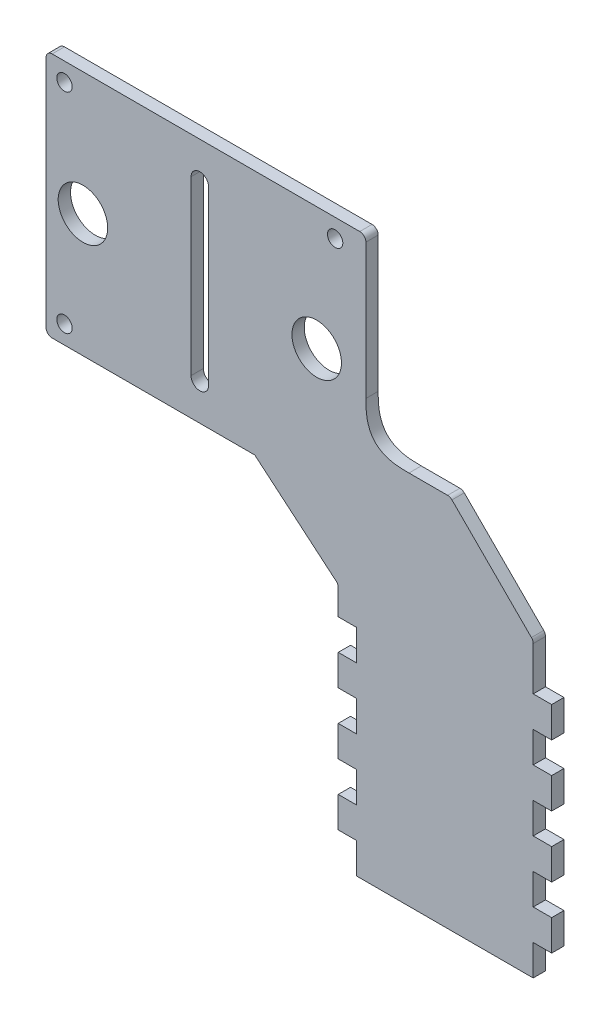
SolidWorks part; units mm, degrees
ref_plane "Front Plane" through (0, 0, 0) normal (0, 0, 1) x (1, 0, 0)
ref_plane "Top Plane" through (0, 0, 0) normal (0, 1, 0) x (1, 0, 0)
ref_plane "Right Plane" through (0, 0, 0) normal (1, 0, 0) x (0, 0, -1)
sketch "Sketch1" plane through (0, 0, 0) normal (0, 0, 1) x (1, 0, 0)
  line L0 (33.9359, 0) -> (47, -11)
  line L1 (0, 0) -> (50, 0)
  line L2 (0, 0) -> (0, 40)
  line L3 (0, 40) -> (50, 40)
  line L4 (50, 0) -> (50, 40)
  line L5 (50, 0) -> (79.2, 0)
  line L6 (50, 0) -> (50, -51)
  line L7 (50, -51) -> (79.2, -51)
  line L8 (79.2, 0) -> (79.2, -51)
  line L9 (50, 0) -> (79.2, 0)
  line L12 (79.2, 0) -> (79.2, -21)
  line L13 (79.2, 0) -> (50, 0)
  line L14 (79.2, 0) -> (79.2, 10)
  line L15 (79.2, 10) -> (50, 10)
  line L16 (50, 0) -> (50, 10)
  line L17 (40, 0) -> (50, 0)
  line L18 (40, 0) -> (40, -5)
  line L19 (40, -5) -> (50, -5)
  line L20 (50, 0) -> (50, -5)
  line L21 (50, -5) -> (44, -5)
  line L22 (50, -5) -> (50, -11)
  line L23 (50, -11) -> (44, -11)
  line L24 (44, -5) -> (44, -11)
  line L26 (50, 10) -> (52, 10)
  line L27 (50, 10) -> (50, 40)
  line L28 (50, 40) -> (52, 40)
  line L29 (52, 10) -> (52, 40)
  dimension "D1" = 50
  dimension "D2" = 40
  dimension "D3" = 29.2
  dimension "D4" = 51
  dimension "D5" = 0
  dimension "D6" = 10
  dimension "D7" = 0
  dimension "D8" = 0
  dimension "D9" = 0
  dimension "D10" = 10
  dimension "D11" = 5
  dimension "D12" = 0
  dimension "D13" = 0
  dimension "D14" = 6
  dimension "D15" = 6
  dimension "D16" = 2
  dimension "D17" = 3
extrude "plate_body" add sketch "Sketch1" along normal blind 2 contours L1 L4 L3 L2 | L8 L5 L1 L6 L7 | L14 L15 L4 L5 | L18 L19 L6 L1 | L19 L6 | L15 L29 L28 L4 | L18 L1 L0 | L24 L19 L0 region at (39.4486, -3.1115, 0) region at (25, 20, 0) region at (47.2353, -7.7462, 0) region at (45, -2.5, 0) region at (64.6, 5, 0) region at (64.6, -25.5, 0) region at (51, 25, 0)
sketch "Sketch2" plane through (0, 0, 2) normal (0, 0, 1) x (1, 0, 0)
  line L2 (0, 0) -> (0, 40) construction
  line L3 (0, 40) -> (52, 40) construction
  circle A0 centre (6, 20) radius 4.0238
  circle A1 centre (44, 20) radius 4.0238
  dimension "D1" = 38
  dimension "D2" = 8.0476
  dimension "D3" = 8.0476
  dimension "D4" = 6
  dimension "D5" = 20
  dimension "D6" = 20
extrude "shaft_bearings" cut sketch "Sketch2" against normal through all
sketch "Sketch4" plane through (0, 0, 2) normal (0, 0, 1) x (1, 0, 0)
  line L0 (25, 34) -> (25, 6) construction
  line L1 (26.425, 34) -> (26.425, 6)
  line L2 (23.575, 34) -> (23.575, 6)
  line L3 (0, 0) -> (33.9359, 0) construction
  line L5 (0, 0) -> (0, 40) construction
  arc A0 (26.425, 34) -> (23.575, 34) centre (25, 34) ccw
  arc A1 (23.575, 6) -> (26.425, 6) centre (25, 6) ccw
  point P2 (25, 20)
  dimension "D4" = 6
  dimension "D1" = 2.85
  dimension "D2" = 28
  dimension "D3" = 25
extrude "slot" cut sketch "Sketch4" against normal through all
sketch "Sketch5" plane through (0, 0, 2) normal (0, 0, 1) x (1, 0, 0)
  line L0 (0, 40) -> (52, 40) construction
  line L1 (0, 0) -> (0, 40) construction
  line L3 (50, 10) -> (50, 40) construction
  line L4 (0, 0) -> (33.9359, 0) construction
  circle A0 centre (3, 37) radius 1.25
  circle A1 centre (47, 37) radius 1.25
  circle A2 centre (3, 3) radius 1.25
  dimension "D1" = 2.5
  dimension "D2" = 2.5
  dimension "D3" = 2.5
  dimension "D5" = 3
  dimension "D6" = 3
  dimension "D7" = 3
  dimension "D8" = 3
  dimension "D11" = 3
  dimension "D12" = 3
extrude "bolt_holes" cut sketch "Sketch5" against normal through all
sketch "Sketch6" plane through (0, 0, 2) normal (0, 0, 1) x (1, 0, 0)
  line L0 (50, -51) -> (79.2, -51) construction
  line L1 (50, -11) -> (50.5, -11)
  line L2 (50, -11) -> (50, -51)
  line L3 (50, -51) -> (50.5, -51)
  line L4 (50.5, -11) -> (50.5, -51)
  line L5 (50, -11) -> (47, -11) construction
  dimension "D1" = 0.5
  dimension "D2" = 0
extrude "Cut-Extrude1" cut sketch "Sketch6" against normal through all
sketch "Sketch8" plane through (0, 0, 2) normal (0, 0, 1) x (1, 0, 0)
  line L0 (50.5, -36) -> (47.5, -36)
  line L1 (50.5, -46) -> (47.5, -46)
  line L2 (50.5, -46) -> (50.5, -41)
  line L3 (50.5, -41) -> (47.5, -41)
  line L4 (47.5, -46) -> (47.5, -41)
  line L5 (79.2, -46) -> (82.2, -46)
  line L6 (79.2, -46) -> (79.2, -41)
  line L7 (79.2, -41) -> (82.2, -41)
  line L8 (82.2, -46) -> (82.2, -41)
  line L9 (50.5, -36) -> (50.5, -31)
  line L10 (50.5, -31) -> (47.5, -31)
  line L11 (47.5, -36) -> (47.5, -31)
  line L12 (79.2, -36) -> (82.2, -36)
  line L13 (79.2, -36) -> (79.2, -31)
  line L14 (79.2, -31) -> (82.2, -31)
  line L15 (82.2, -36) -> (82.2, -31)
  line L16 (50.5, -51) -> (50.5, -11) construction
  line L17 (79.2, -51) -> (79.2, 10) construction
  line L18 (50.5, -16) -> (47.5, -16)
  line L19 (50.5, -26) -> (47.5, -26)
  line L20 (50.5, -26) -> (50.5, -21)
  line L21 (50.5, -21) -> (47.5, -21)
  line L22 (47.5, -26) -> (47.5, -21)
  line L23 (79.2, -26) -> (82.2, -26)
  line L24 (79.2, -26) -> (79.2, -21)
  line L25 (79.2, -21) -> (82.2, -21)
  line L26 (82.2, -26) -> (82.2, -21)
  line L27 (50.5, -16) -> (50.5, -11)
  line L28 (50.5, -11) -> (47.5, -11)
  line L29 (47.5, -16) -> (47.5, -11)
  line L30 (79.2, -16) -> (82.2, -16)
  line L31 (79.2, -16) -> (79.2, -11)
  line L32 (79.2, -11) -> (82.2, -11)
  line L33 (82.2, -16) -> (82.2, -11)
  line L34 (50.5, -51) -> (79.2, -51) construction
  point P38 (80.7, -31)
  point P41 (80.7, -41)
  dimension "D1" = 5
  dimension "D2" = 5
  dimension "D3" = 3
  dimension "D4" = 3
  dimension "D5" = 5
  dimension "D6" = 5
  dimension "D7" = 3
  dimension "D8" = 3
  dimension "D9" = 0
  dimension "D10" = 0
  dimension "D11" = 5
  dimension "D12" = 5
  dimension "D13" = 5
  dimension "D14" = 5
  dimension "D15" = 3
  dimension "D16" = 3
  dimension "D17" = 5
  dimension "D18" = 5
  dimension "D19" = 3
  dimension "D20" = 3
  dimension "D21" = 5
  dimension "D22" = 5
  dimension "D25" = 0
  dimension "D26" = 0
  dimension "D27" = 5
  dimension "D28" = 5
  dimension "D29" = 10
  dimension "D30" = 10
extrude "finger_joints" add sketch "Sketch8" along direction (0, 0, 1) on the side against the normal up to surface (2 mm away) up to face at (4.25, 3, 0)
sketch "Sketch9" plane through (0, 0, 2) normal (0, 0, 1) x (1, 0, 0)
  line L0 (50.5, -51) -> (79.2, -51) construction
  line L1 (57, -21) -> (67, -21)
  line L2 (57, -21) -> (57, -41)
  line L3 (57, -41) -> (67, -41)
  line L4 (67, -21) -> (67, -41)
  line L5 (50.5, -51) -> (50.5, -46) construction
  dimension "D1" = 10
  dimension "D2" = 20
  dimension "D3" = 10
  dimension "D4" = 6.5
extrude "Cut-Extrude2" [suppressed] cut sketch "Sketch9" against normal through all
sketch "Sketch10" plane through (0, 0, 2) normal (0, 0, 1) x (1, 0, 0)
  line L0 (0, 40) -> (52, 40) construction
  line L1 (9.3, 40) -> (24.3, 40)
  line L2 (9.3, 40) -> (9.3, 50)
  line L3 (9.3, 50) -> (24.3, 50)
  line L4 (24.3, 40) -> (24.3, 50)
  circle A0 centre (16.8, 45) radius 1.5
  arc A1 (26.425, 34) -> (23.575, 34) centre (25, 34) ccw construction
  point P11 (25, 35.425)
  dimension "D4" = 7.5
  dimension "D5" = 5
  dimension "D6" = 3
  dimension "D3" = 8.2
  dimension "D1" = 10
  dimension "D2" = 15
extrude "tail_rod_mount" [suppressed] add sketch "Sketch10" against normal up to surface (2 mm away) up to face at (60.4634, -22.85, 0)
sketch "Sketch12" plane through (0, 0, 2) normal (0, 0, 1) x (1, 0, 0)
  line L0 (65.7, 10) -> (79.2, -3.5)
  line L1 (79.2, 10) -> (65.7, 10)
  line L2 (79.2, 10) -> (79.2, -3.5)
  line L3 (79.2, -3.5) -> (65.7, -3.5)
  line L4 (65.7, 10) -> (65.7, -3.5)
  point P5 (79.2, 3.25)
  dimension "D1" = 13.5
  dimension "D2" = 13.5
extrude "Cut-Extrude3" cut sketch "Sketch12" against normal blind 10 contours L2 L1 L0 region at (74.7, 5.5, 2)
fillet "1mm_fillets" radius 1 6 edges at (0, 0, 1) (0, 40, 1) (79.2, -3.5, 1) (65.7, 10, 1) (52, 40, 1) (47.5, -11, 1)
fillet "Fillet1" radius 7 1 edges at (52, 10, 1) curvature continuous yes
